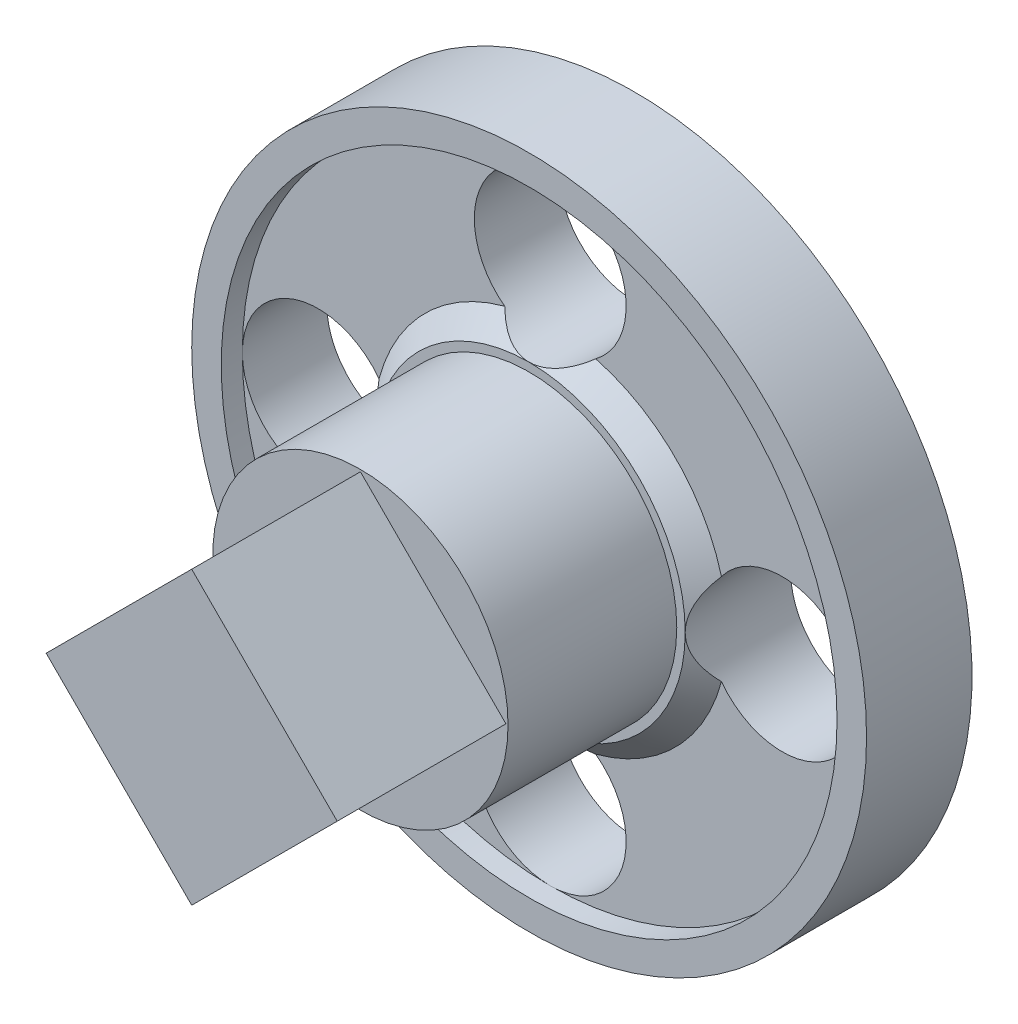
SolidWorks part; units mm, degrees
ref_plane "前视基准面" through (0, 0, 0) normal (0, 0, 1) x (1, 0, 0)
ref_plane "上视基准面" through (0, 0, 0) normal (0, 1, 0) x (1, 0, 0)
ref_plane "右视基准面" through (0, 0, 0) normal (1, 0, 0) x (0, 0, -1)
other "Configuration Table"
sketch "草图1" plane through (0, 0, 0) normal (0, 0, 1) x (1, 0, 0)
  circle A1 centre (0, 5.5) radius 1.8
  circle A2 centre (5.5, 0) radius 1.8
  circle A3 centre (0, -5.5) radius 1.8
  circle A4 centre (-5.5, 0) radius 1.8
  circle A5 centre (0, 0) radius 9
  point P12 (0, 0)
  dimension "D1" = 4
extrude "凸台-拉伸1" add sketch "草图1" along normal blind 3
sketch "草图2" plane through (0, 0, 3) normal (0, 0, 1) x (1, 0, 0)
  circle A0 centre (0, 0) radius 2.5
extrude "凸台-拉伸2" add sketch "草图2" along normal blind 5
sketch "草图3" plane through (0, 0, 3) normal (0, 0, 1) x (1, 0, 0)
  circle A0 centre (0, 0) radius 3
extrude "凸台-拉伸3" add sketch "草图3" along normal blind 1
sketch "草图4" plane through (0, 0, 8) normal (0, 0, 1) x (1, 0, 0)
  line L0 (1.9887, 4.8677) -> (2.4855, 0.2685)
  line L2 (-2.5, 0) -> (-1.9884, 4.8651)
  circle A1 centre (0.0003, 4.6529) radius 0.75
  arc A2 (1.9887, 4.8677) -> (-1.989, 4.8592) centre (0.0003, 4.6529) ccw
  arc A3 (-2.4453, 0.52) -> (2.4855, 0.2685) centre (0, 0) ccw
  circle M1 centre (0, 0) radius 2.5
extrude "凸台-拉伸4" add sketch "草图4" along normal blind 1 and the other way blind 1 contours L0 A2 L2 A1 M1 | L2 M1 region at (2.1569, 2.5594, 8) region at (0.0006, -0.0001, 8)
sketch "草图5" plane through (0, 0, 7) normal (0, 0, -1) x (-1, 0, 0)
  line L0 (0, 2.4816) -> (2.5, 0)
  line L1 (2.5, 0) -> (0, -2.5)
  line L2 (0, -2.5) -> (-2.5, 0)
  line L3 (-2.5, 0) -> (0, 2.4816)
  circle A0 centre (0, 0) radius 2.5 construction
  arc A1 (-2.4855, 0.2685) -> (2.5, 0) centre (0, 0) ccw construction
  circle A2 centre (0, 0) radius 11.7748
extrude "切除-拉伸1" cut sketch "草图5" against normal blind 10
sketch "草图6" plane through (0, 0, 9) normal (0, 0, 1) x (1, 0, 0)
  line L0 (0, 2.5) -> (-2.5, 0)
  line L1 (-2.5, 0) -> (0, -2.5)
  line L2 (0, -2.5) -> (2.5, 0)
  line L3 (2.5, 0) -> (0, 2.5)
  arc A0 (2.5, 0) -> (-2.5, 0) centre (0, 0) ccw construction
extrude "凸台-拉伸5" add sketch "草图6" along normal blind 2
sketch "草图7" plane through (0, 0, 9) normal (0, 0, -1) x (-1, 0, 0)
  line L0 (0, 2.4816) -> (-2.5, 0)
  line L1 (-2.5, 0) -> (-8.2577, 6.6447)
  line L2 (-8.2577, 6.6447) -> (8.3249, 1.809)
  line L3 (8.3249, 1.809) -> (0.9015, -7.2466)
  line L4 (0.9015, -7.2466) -> (2.5, 0)
  line L5 (2.5, 0) -> (0, 2.4816)
extrude "切除-拉伸2" cut sketch "草图7" against normal blind 2
sketch "草图8" plane through (0, 0, 0) normal (0, 0, -1) x (-1, 0, 0)
  circle A0 centre (0, 0) radius 8
  circle A1 centre (-0.2386, 0) radius 14.8551
extrude "切除-拉伸3" cut sketch "草图8" against normal blind 10
sketch "草图9" plane through (0, 0, 4) normal (0, 0, 1) x (1, 0, 0)
  circle A0 centre (0, 0) radius 2.5
  circle A1 centre (0, 0.1202) radius 4.2565
extrude "切除-拉伸4" cut sketch "草图9" against normal blind 0.5
sketch "草图10" plane through (0, 0, 3.5) normal (0, 0, 1) x (1, 0, 0)
  circle A0 centre (0, 0) radius 3.45
extrude "凸台-拉伸6" add sketch "草图10" along normal blind 3.5
sketch "草图11" plane through (0, 0, 3.5) normal (0, 0, -1) x (-1, 0, 0)
  circle A0 centre (0, 0) radius 3.7
extrude "凸台-拉伸7" add sketch "草图11" along normal blind 3.5
chamfer "倒角1" distance 0.5 angle 45 4 edges at (2.6163, -2.6163, 3) (2.6163, 2.6163, 3) (-2.6163, -2.6163, 3) (-2.6163, 2.6163, 3)
sketch "草图12" plane through (0, 0, 7) normal (0, 0, 1) x (1, 0, 0)
  line L0 (0, 3.45) -> (-3.45, 0)
  line L1 (-3.45, 0) -> (0, -3.45)
  line L2 (0, -3.45) -> (3.45, 0)
  line L3 (3.45, 0) -> (0, 3.45)
  circle A0 centre (0, 0) radius 3.45 construction
  circle A1 centre (0, 0) radius 3.45 construction
extrude "凸台-拉伸8" add sketch "草图12" along normal blind 4
sketch "草图13" plane through (0, 0, 3) normal (0, 0, 1) x (1, 0, 0)
  circle A0 centre (0, 0) radius 4.2
  circle A1 centre (0, 0) radius 3.45
extrude "切除-拉伸5" cut sketch "草图13" along normal blind 3
sketch "草图14" plane through (0, 0, 3) normal (0, 0, 1) x (1, 0, 0)
  circle A0 centre (0, 0) radius 3.7
  circle A1 centre (0, 0) radius 6
extrude "切除-拉伸6" cut sketch "草图14" against normal blind 0.5
chamfer "倒角2" distance 0.5 angle 45 4 edges at (2.6163, 2.6163, 2.5) (-2.6163, 2.6163, 2.5) (-2.6163, -2.6163, 2.5) (2.6163, -2.6163, 2.5)
chamfer "倒角3" distance 0.5 angle 45 4 edges at (4.2426, -4.2426, 2.5) (-4.2426, -4.2426, 2.5) (4.2426, 4.2426, 2.5) (-4.2426, 4.2426, 2.5)
sketch "草图15" plane through (0, 0, 3) normal (0, 0, 1) x (1, 0, 0)
  circle A0 centre (0, 0) radius 3.5
extrude "凸台-拉伸9" add sketch "草图15" along normal blind 4
sketch "草图16" plane through (0, 0, 2.5) normal (0, 0, 1) x (1, 0, 0)
  circle A0 centre (0.1543, 0) radius 4.5063
  circle A1 centre (0, 0) radius 7.3
extrude "切除-拉伸7" cut sketch "草图16" along normal blind 3
sketch "草图19" plane through (0, 0, 0) normal (0, 0, -1) x (-1, 0, 0)
  circle A0 centre (0, 0) radius 10.0673
extrude "切除-拉伸9" cut sketch "草图19" against normal blind 0.5
